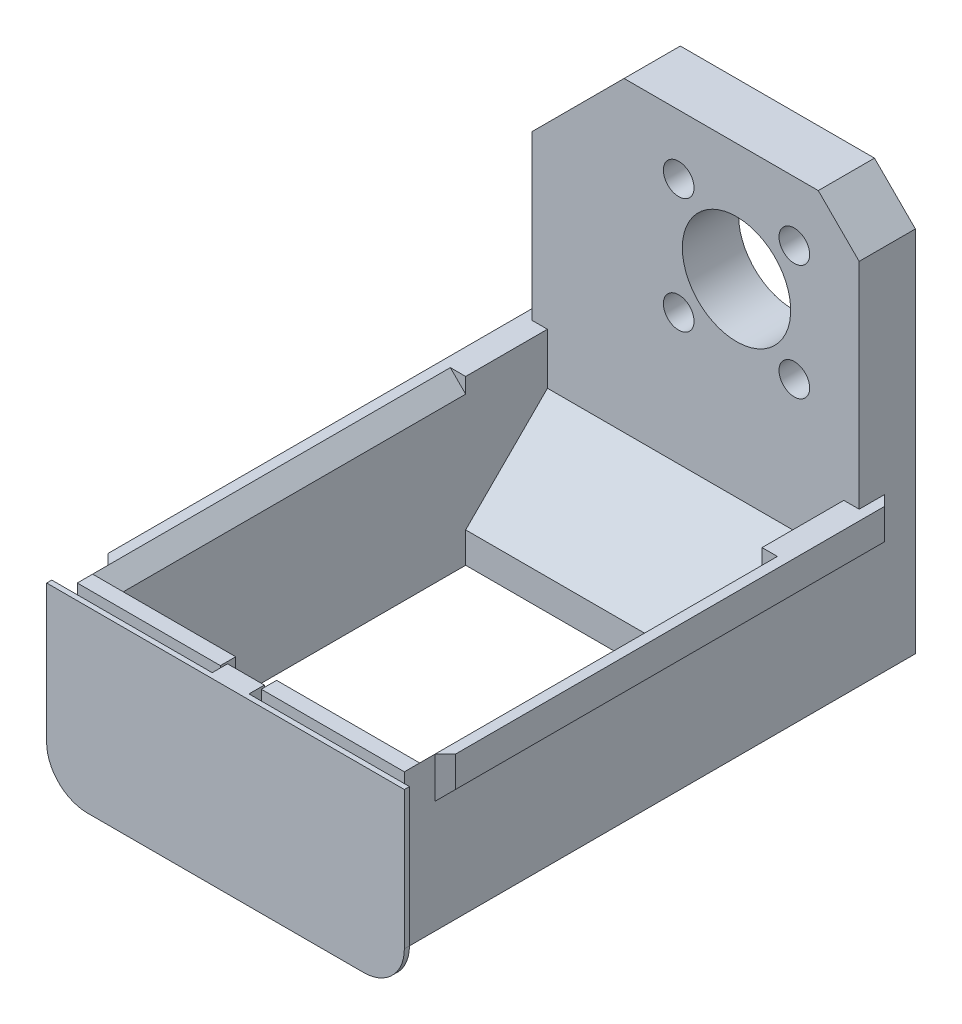
SolidWorks part; units mm, degrees
ref_plane "Płaszczyzna przednia" through (0, 0, 0) normal (0, 0, 1) x (1, 0, 0)
ref_plane "Płaszczyzna górna" through (0, 0, 0) normal (0, 1, 0) x (1, 0, 0)
ref_plane "Płaszczyzna prawa" through (0, 0, 0) normal (1, 0, 0) x (0, 0, -1)
sketch "Szkic1" plane through (0, 0, 0) normal (0, 1, 0) x (1, 0, 0)
  line L1 (-17, 25) -> (17, 25)
  line L2 (-17, 25) -> (-17, -25)
  line L3 (-17, -25) -> (17, -25)
  line L4 (17, 25) -> (17, -25)
  line L5 (-17, 25) -> (17, -25) construction
  line L6 (-17, -25) -> (17, 25) construction
  point P0 (0, 0)
  dimension "D1" = 34
  dimension "D2" = 50
extrude "Dodanie-wyciągnięcie1" add sketch "Szkic1" along normal blind 17
sketch "Szkic3" plane through (0, 17, 0) normal (0, 1, 0) x (1, 0, 0)
  line L0 (17, -25) -> (17, 25) construction
  line L1 (17, 25) -> (-17, 25)
  line L2 (17, 25) -> (17, 19.5)
  line L3 (17, 19.5) -> (-17, 19.5)
  line L4 (-17, 25) -> (-17, 19.5)
  line L5 (17, 25) -> (-17, 25) construction
  line L6 (-17, 25) -> (-17, -25) construction
  line L7 (-17, -25) -> (17, -25) construction
  dimension "D1" = 44.5
extrude "Dodanie-wyciągnięcie2" add sketch "Szkic3" along normal blind 25
sketch "Szkic4" plane through (0, 0, -25) normal (0, 0, -1) x (-1, 0, 0)
  line L1 (-4, 30.5) -> (-9.6569, 36.1569) construction
  line L2 (-4, 30.5) -> (-4, 38.5) construction
  line L3 (-17, 42) -> (17, 42) construction
  line L4 (0, 0) -> (0, 62.7345) construction
  line L6 (-17, 0) -> (17, 0) construction
  circle A0 centre (1.6569, 36.1569) radius 1.5
  circle A1 centre (-4, 30.5) radius 5.3
  circle A2 centre (-4, 30.5) radius 8
  circle A3 centre (-9.6569, 36.1569) radius 1.5
  circle A4 centre (-4, 30.5) radius 8
  circle A5 centre (1.6569, 24.8431) radius 1.5
  circle A6 centre (-4, 30.5) radius 8
  circle A7 centre (-9.6569, 24.8431) radius 1.5
  circle A8 centre (-4, 30.5) radius 8
  point P21 (-4, 30.5)
  dimension "D1" = 4
  dimension "D2" = 11.5
  dimension "D3" = 10.6
  dimension "D4" = 16
  dimension "D5" = 3
  dimension "D6" = 45
  dimension "D7" = 4
extrude "Wytnij-wyciągnięcie2" cut sketch "Szkic4" against normal blind 25 contours A2 A3 | A2 A3 | A2 A0 | A0 A2 | A6 A7 | A6 A7 | A4 A5 | A4 A5 | A1 region at (-2.0886, 36.5886, -25) region at (-1.1893, 35.6893, -25) region at (9.1893, 35.6893, -25) region at (10.0886, 36.5886, -25) region at (-2.0886, 24.4114, -25) region at (-1.1893, 25.3107, -25) region at (9.1893, 25.3107, -25) region at (10.0886, 24.4114, -25) region at (4, 30.5, -25)
chamfer "Sfazowanie1" distance 10 angle 45 1 edges at (-17, 42, -22.25)
chamfer "Sfazowanie2" distance 5 angle 45 1 edges at (17, 42, -22.25)
sketch "Szkic5" plane through (0, 0, 25) normal (0, 0, 1) x (1, 0, 0)
  line L0 (-17, 17) -> (-17, 0) construction
  line L1 (-17, 14) -> (-16, 14)
  line L2 (-17, 14) -> (-17, 0)
  line L3 (-17, 0) -> (-16, 0)
  line L4 (-16, 14) -> (-16, 0)
  line L5 (-17, 0) -> (17, 0) construction
  line L6 (17, 17) -> (17, 0) construction
  line L7 (17, 14) -> (16, 14)
  line L8 (17, 14) -> (17, 0)
  line L9 (17, 0) -> (16, 0)
  line L10 (16, 14) -> (16, 0)
  line L11 (-17, 17) -> (17, 17) construction
  line L12 (-17, 17) -> (-16, 17)
  line L13 (-17, 17) -> (-17, 42)
  line L14 (-17, 42) -> (-16, 42)
  line L15 (-16, 17) -> (-16, 42)
  line L16 (17, 17) -> (16, 17)
  line L17 (17, 17) -> (17, 42)
  line L18 (17, 42) -> (16, 42)
  line L19 (16, 17) -> (16, 42)
  line L20 (-17, 17) -> (17, 17) construction
  line L21 (-7, 42) -> (12, 42) construction
  line L23 (-16, 0) -> (16, 0)
  line L24 (-16, 0) -> (-16, 1)
  line L25 (-16, 1) -> (16, 1)
  line L26 (16, 0) -> (16, 1)
  line M14 (-17, 0) -> (17, 0)
  line M16 (17, 17) -> (-17, 17)
  line M17 (-17, 17) -> (-17, 0)
  dimension "D1" = 1
  dimension "D2" = 3
  dimension "D3" = 1
extrude "Wytnij-wyciągnięcie3" cut sketch "Szkic5" against normal blind 68 contours L25 L4 L10 M14 | L4 L1 M17 M14 | L15 L14 L13 M16 | L9 L8 L7 L10 | L17 L18 L19 L16 region at (-16.5, 7, 25) region at (-16.5, 29.5, 25) region at (0, 0.5, 25)
chamfer "Sfazowanie3" distance 1 angle 45 2 edges at (-16, 14, 0) (16, 14, 0)
chamfer "Sfazowanie4" distance 1 angle 45 2 edges at (-16, 1, 0) (16, 1, 0)
ref_plane "Płaszczyzna1" through (0, 0, 26) normal (0, 0, 1) x (1, 0, 0)
sketch "Szkic7" plane through (0, 0, 26) normal (0, 0, 1) x (1, 0, 0)
  line L0 (0, 17) -> (0, 1) construction
  line L1 (-17, 17) -> (17, 17) construction
  line L2 (-15, 1) -> (15, 1) construction
  line L3 (17, 17) -> (17, 14) construction
  line L4 (17.5, -0.5) -> (-17.5, -0.5)
  line L5 (17.5, -0.5) -> (17.5, 17)
  line L6 (17.5, 17) -> (-17.5, 17)
  line L7 (-17.5, -0.5) -> (-17.5, 17)
  line L8 (17.5, -0.5) -> (-17.5, 17) construction
  line L9 (17.5, 17) -> (-17.5, -0.5) construction
  point P6 (0, 8.25)
  dimension "D1" = 0.5
  dimension "D2" = 1.5
extrude "Dodanie-wyciągnięcie3" add sketch "Szkic7" along normal blind 0.5 separate body
fillet "Zaokrąglenie3" radius 4 2 edges at (17.5, -0.5, 26.25) (-17.5, -0.5, 26.25)
sketch "Szkic8" plane through (0, 17, 0) normal (0, 1, 0) x (1, 0, 0)
  line L0 (-16, 25) -> (-17, 25) construction
  line L1 (-17, 25) -> (-16, 25)
  line L2 (-17, 25) -> (-17, 22)
  line L3 (-17, 22) -> (-16, 22)
  line L4 (-16, 25) -> (-16, 22)
  line L5 (17, 25) -> (16, 25)
  line L6 (17, 25) -> (17, 22)
  line L7 (17, 22) -> (16, 22)
  line L8 (16, 25) -> (16, 22)
  line L9 (-17, -25) -> (-16, -25)
  line L10 (-17, -25) -> (-17, -22)
  line L11 (-17, -22) -> (-16, -22)
  line L12 (-16, -25) -> (-16, -22)
  line L13 (17, -25) -> (16, -25)
  line L14 (17, -25) -> (17, -22)
  line L15 (17, -22) -> (16, -22)
  line L16 (16, -25) -> (16, -22)
  point P20 (0, 0)
  point P22 (-16.0662, 25)
  dimension "D1" = 1
  dimension "D2" = 3
extrude "Wytnij-wyciągnięcie4" cut sketch "Szkic8" against normal blind 68
chamfer "Sfazowanie6" distance 1 angle 45 4 edges at (-17, 15.5, -22) (17, 15.5, -22) (17, 15.5, 22) (-17, 15.5, 22)
sketch "Szkic9" plane through (0, 17, 0) normal (0, 1, 0) x (1, 0, 0)
  line L0 (0, -25) -> (0, 25) construction
  line L1 (-16, -25) -> (16, -25) construction
  line L2 (12, 25) -> (-7, 25) construction
  line L3 (-16, -25) -> (-16, -22) construction
  line L4 (14.5, 11.5) -> (-14.5, 11.5)
  line L5 (14.5, 11.5) -> (14.5, -23.5)
  line L6 (14.5, -23.5) -> (-14.5, -23.5)
  line L7 (-14.5, 11.5) -> (-14.5, -23.5)
  line L8 (14.5, 11.5) -> (-14.5, -23.5) construction
  line L9 (14.5, -23.5) -> (-14.5, 11.5) construction
  point P7 (0, -6)
  point P14 (-14.5, 13.3185)
  dimension "D1" = 1.5
  dimension "D2" = 1.5
  dimension "D3" = 35
extrude "Wytnij-wyciągnięcie5" cut sketch "Szkic9" against normal blind 68
chamfer "Sfazowanie7" distance 1.5 angle 45 2 edges at (14.5, 17, 6) (-14.5, 17, 6)
sketch "Szkic10" plane through (0, 0, 25) normal (0, 0, 1) x (1, 0, 0)
  line L0 (-16, 17) -> (16, 17) construction
  line L1 (-2, 19) -> (2, 19)
  line L2 (-2, 19) -> (-2, 15)
  line L3 (-2, 15) -> (2, 15)
  line L4 (2, 19) -> (2, 15)
  line L5 (-2, 19) -> (2, 15) construction
  line L6 (-2, 15) -> (2, 19) construction
  point P0 (0, 17)
  dimension "D1" = 4
  dimension "D2" = 4
extrude "Wytnij-wyciągnięcie6" cut sketch "Szkic10" against normal blind 10
sketch "Szkic11" plane through (0, 0, 26) normal (0, 0, -1) x (-1, 0, 0)
  line L0 (-17.5, 17) -> (17.5, 17) construction
  line L1 (-1.8, 18.8) -> (1.8, 18.8)
  line L2 (-1.8, 18.8) -> (-1.8, 15.2)
  line L3 (-1.8, 15.2) -> (1.8, 15.2)
  line L4 (1.8, 18.8) -> (1.8, 15.2)
  line L5 (-1.8, 18.8) -> (1.8, 15.2) construction
  line L6 (-1.8, 15.2) -> (1.8, 18.8) construction
  line L7 (-1.8, 17) -> (1.8, 17)
  point P0 (0, 17)
  line M10 (17.5, 17) -> (-17.5, 17)
  dimension "D1" = 3.6
  dimension "D2" = 3.6
extrude "Dodanie-wyciągnięcie4" add sketch "Szkic11" along normal blind 1.5 contours L4 L2 L3 M10 region at (0, 16.1, 26)
sketch "Szkic12" plane through (0, 0, -11.5) normal (0, 0, 1) x (1, 0, 0)
  line L0 (16, 17) -> (-16, 17) construction
  line L1 (14.5, 22) -> (-14.5, 22)
  line L2 (14.5, 22) -> (14.5, 12)
  line L3 (14.5, 12) -> (-14.5, 12)
  line L4 (-14.5, 22) -> (-14.5, 12)
  line L5 (14.5, 22) -> (-14.5, 12) construction
  line L6 (14.5, 12) -> (-14.5, 22) construction
  line L7 (-14.5, 1) -> (-14.5, 15.5) construction
  point P0 (0, 17)
  dimension "D1" = 10
extrude "Wytnij-wyciągnięcie7" cut sketch "Szkic12" against normal up to vertex (8 mm away) up to point (16, 17, -19.5)
chamfer "Sfazowanie8" distance 8 angle 45 1 edges at (0, 12, -11.5)
sketch "Szkic13" plane through (0, 0, -25) normal (0, 0, -1) x (-1, 0, 0)
  line L0 (-2, 15) -> (-2, 17) construction
  line L1 (2, 17) -> (2, 15) construction
  line L2 (-2, 15) -> (-2, 17)
  line L3 (2, 17) -> (2, 15)
  line L5 (-2, 17) -> (2, 17)
  line L6 (-2, 17) -> (-2, 15)
  line L7 (-2, 15) -> (2, 15)
  line L8 (2, 17) -> (2, 15)
extrude "Wytnij-wyciągnięcie8" cut sketch "Szkic13" against normal blind 2 contours L2 L7 L3 L5 region at (0, 16, -25)
